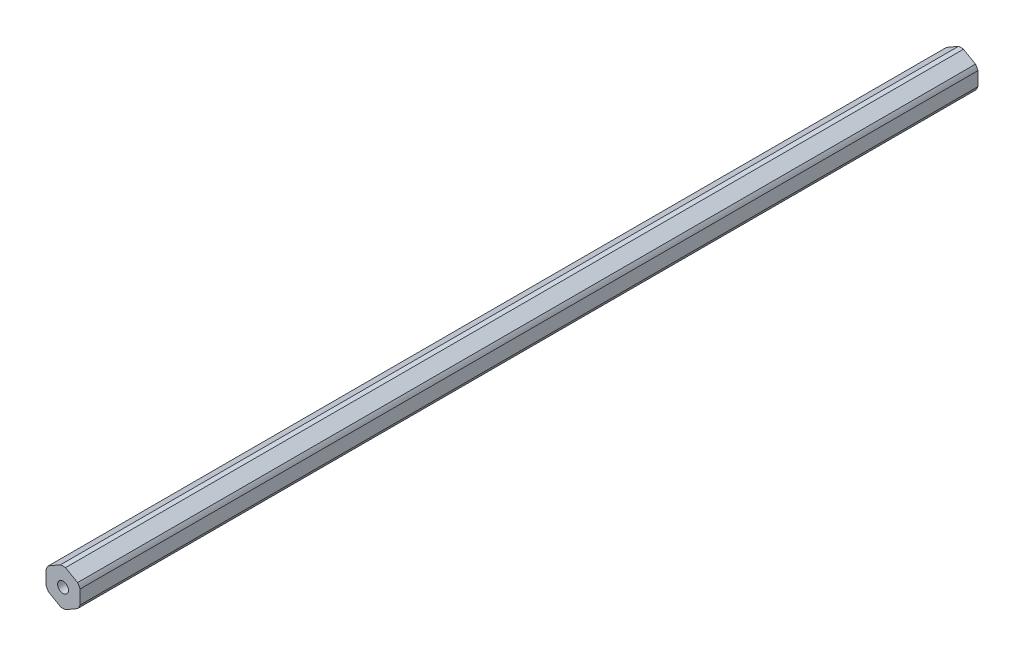
SolidWorks part; units mm, degrees
ref_plane "Front Plane" through (0, 0, 0) normal (0, 0, 1) x (1, 0, 0)
ref_plane "Top Plane" through (0, 0, 0) normal (0, 1, 0) x (1, 0, 0)
ref_plane "Right Plane" through (0, 0, 0) normal (1, 0, 0) x (0, 0, -1)
sketch "Sketch1" plane through (0, 0, 0) normal (0, 0, 1) x (1, 0, 0)
  line L1 (0, 7.3323) -> (-6.35, 3.6662)
  line L2 (-6.35, 3.6662) -> (-6.35, -3.6662)
  line L3 (-6.35, -3.6662) -> (0, -7.3323)
  line L4 (0, -7.3323) -> (6.35, -3.6662)
  line L5 (6.35, -3.6662) -> (6.35, 3.6662)
  line L6 (6.35, 3.6662) -> (0, 7.3323)
  circle A0 centre (0, 0) radius 6.35 construction
  circle A1 centre (0, 0) radius 6.858
  dimension "D1" = 12.7
  dimension "D2" = 13.716
extrude "Boss-Extrude1" add sketch "Sketch1" along normal mid plane 334.9625 contours L5 A1 L6 L1 L2 L3 L4 region at (0, 0, 0)
hole_wizard "#10-32 Tapped Hole1" positions "3DSketch1" profile "Sketch2" tap size "#10-32" standard "ANSI Inch"
sketch3d "3DSketch1"
  line L0 (0, 0, 167.4812) -> (0, 0, -167.4812) construction
  line L1 (0, 0, 167.4812) -> (0, 0, -167.4812) construction
  point P0 (0, 0, 167.4812)
  point P4 (0, 0, -167.4812)
sketch "Sketch2" plane through (0, 0, 167.4812) normal (1, 0, 0) x (0, -1, 0)
  line L0 (0, 0) -> (0, 17.5608)
  line L1 (0, 17.5608) -> (2.0193, 16.3474)
  line L2 (2.0193, 16.3474) -> (2.0193, 0)
  line L5 (2.0193, 0) -> (0, 0)
  line L10 (0, 17.5608) -> (-2.0193, 16.3474) construction
  line L11 (0, -6.35) -> (0, 107.95) construction
  dimension "Tap Drill Dia." = 4.0386
  dimension "Tap Drill Depth" = 16.3474
  dimension "Drill Angle" = 118
cosmetic thread "Hole Thread1" parameters "D1"=13.97, "D2"=4.826
cosmetic thread "Hole Thread2" parameters "D1"=13.97, "D2"=4.826
